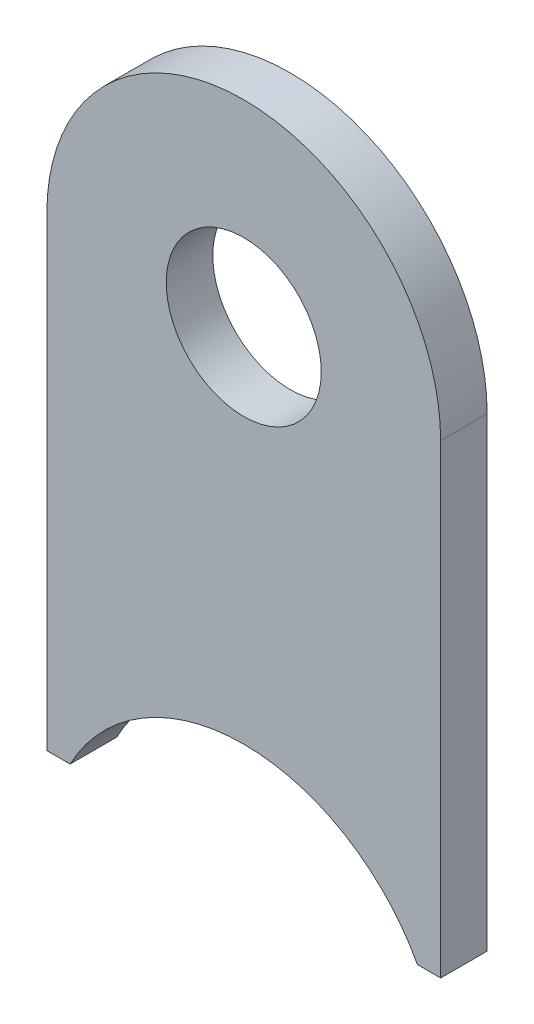
SolidWorks part; units mm, degrees
ref_plane "Front Plane" through (0, 0, 0) normal (0, 0, 1) x (1, 0, 0)
ref_plane "Top Plane" through (0, 0, 0) normal (0, 1, 0) x (1, 0, 0)
ref_plane "Right Plane" through (0, 0, 0) normal (1, 0, 0) x (0, 0, -1)
sketch "Sketch1" plane through (0, 0, 0) normal (0, 0, 1) x (1, 0, 0)
  line L0 (-12.7, 0) -> (-12.7, -30.0125)
  line L1 (12.7, 0) -> (12.7, -30.0125)
  line L2 (-12.7, -30.0125) -> (-11.2, -30.0125)
  line L3 (11.2, -30.0125) -> (12.7, -30.0125)
  circle A0 centre (0, 0) radius 5
  arc A1 (-12.7, 0) -> (12.7, 0) centre (0, 0) cw
  arc A2 (-11.2, -30.0125) -> (11.2, -30.0125) centre (0, -36) cw
  dimension "D1" = 10
  dimension "D2" = 36
  dimension "D3" = 12.7
  dimension "D4" = 1.5
extrude "Boss-Extrude1" add sketch "Sketch1" along normal blind 1.5 and the other way blind 1.5
